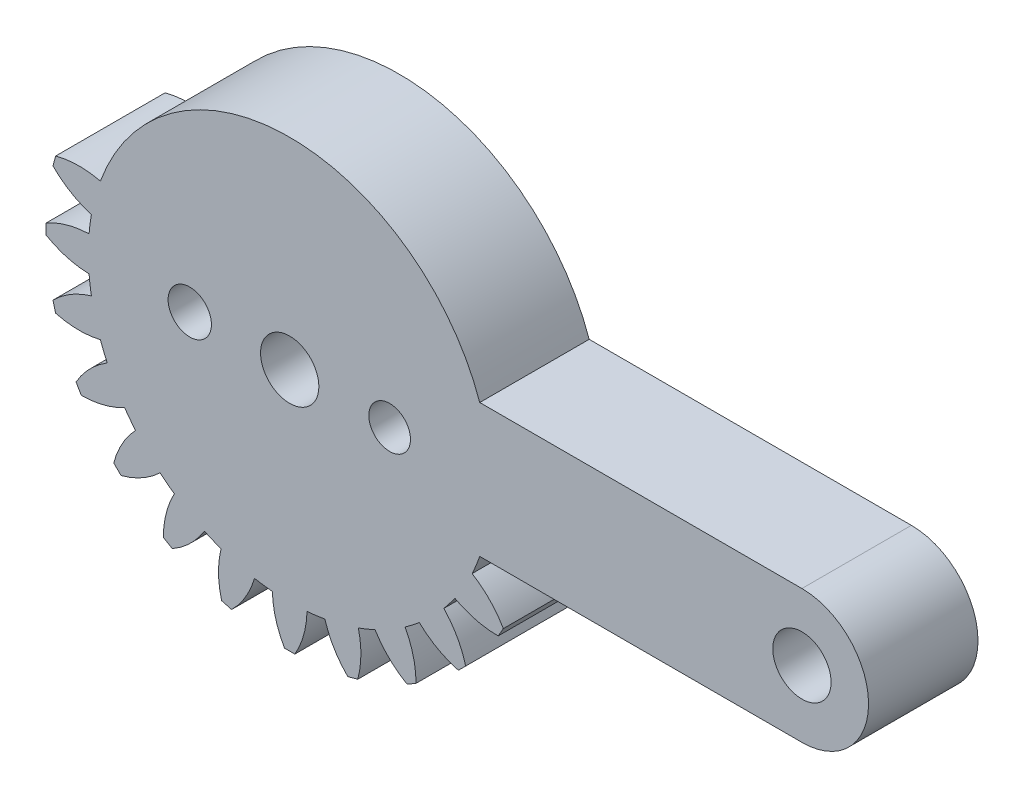
SolidWorks part; units mm, degrees
ref_plane "Front Plane" through (0, 0, 0) normal (0, 0, 1) x (1, 0, 0)
ref_plane "Top Plane" through (0, 0, 0) normal (0, 1, 0) x (1, 0, 0)
ref_plane "Right Plane" through (0, 0, 0) normal (1, 0, 0) x (0, 0, -1)
sketch "Sketch2" plane through (0, 0, 0) normal (0, 0, 1) x (1, 0, 0)
  line L0 (0, 0) -> (30.75, 0) construction
  line L1 (0, -14.63) -> (0, 14.63) construction
  line L2 (-0.31, 14.63) -> (0.31, 14.63)
  line L3 (3.4871, 14.2117) -> (4.086, 14.0513)
  line L4 (7.0465, 12.825) -> (7.5835, 12.515)
  line L5 (10.1258, 10.5642) -> (10.5642, 10.1258)
  line L6 (12.515, 7.5835) -> (12.825, 7.0465)
  line L7 (14.0513, 4.086) -> (14.2117, 3.4871)
  line L8 (14.63, 0.31) -> (14.63, -0.31)
  line L9 (14.2117, -3.4871) -> (14.0513, -4.086)
  line L10 (12.825, -7.0465) -> (12.515, -7.5835)
  line L11 (10.5642, -10.1258) -> (10.1258, -10.5642)
  line L12 (7.5835, -12.515) -> (7.0465, -12.825)
  line L13 (4.086, -14.0513) -> (3.4871, -14.2117)
  line L14 (0.31, -14.63) -> (-0.31, -14.63)
  line L15 (-3.4871, -14.2117) -> (-4.086, -14.0513)
  line L16 (-7.0465, -12.825) -> (-7.5835, -12.515)
  line L17 (-10.1258, -10.5642) -> (-10.5642, -10.1258)
  line L18 (-12.515, -7.5835) -> (-12.825, -7.0465)
  line L19 (-14.0513, -4.086) -> (-14.2117, -3.4871)
  line L20 (-14.63, -0.31) -> (-14.63, 0.31)
  line L21 (-14.2117, 3.4871) -> (-14.0513, 4.086)
  line L22 (-12.825, 7.0465) -> (-12.515, 7.5835)
  line L23 (-10.5642, 10.1258) -> (-10.1258, 10.5642)
  line L24 (-7.5835, 12.515) -> (-7.0465, 12.825)
  line L25 (-4.086, 14.0513) -> (-3.4871, 14.2117)
  line L26 (30.75, -4) -> (30.75, 4) construction
  line L27 (30.75, 4) -> (11.4091, 4)
  line L28 (30.75, -4) -> (11.4091, -4)
  circle A0 centre (0, 0) radius 1.75
  circle A1 centre (0, 0) radius 12.09
  circle A2 centre (30.75, 0) radius 1.75
  arc A3 (-1.04, 12.0452) -> (-0.31, 14.63) centre (4.3585, 11.9161) cw
  arc A4 (1.04, 12.0452) -> (0.31, 14.63) centre (-4.3585, 11.9161) ccw
  arc A5 (4.1221, 11.3656) -> (4.086, 14.0513) centre (-1.1258, 12.6381) ccw
  arc A6 (2.113, 11.9039) -> (3.4871, 14.2117) centre (7.294, 10.382) cw
  arc A7 (6.9233, 9.9114) -> (7.5835, 12.515) centre (2.1835, 12.4988) ccw
  arc A8 (5.1219, 10.9514) -> (7.0465, 12.825) centre (9.7326, 8.1404) cw
  arc A9 (9.2526, 7.7818) -> (10.5642, 10.1258) centre (5.344, 11.5078) ccw
  arc A10 (7.7818, 9.2526) -> (10.1258, 10.5642) centre (11.5078, 5.344) cw
  arc A11 (10.9514, 5.1219) -> (12.825, 7.0465) centre (8.1404, 9.7326) ccw
  arc A12 (9.9114, 6.9233) -> (12.515, 7.5835) centre (12.4988, 2.1835) cw
  arc A13 (11.9039, 2.113) -> (14.2117, 3.4871) centre (10.382, 7.294) ccw
  arc A14 (11.3656, 4.1221) -> (14.0513, 4.086) centre (12.6381, -1.1258) cw
  arc A15 (12.0452, -1.04) -> (14.63, -0.31) centre (11.9161, 4.3585) ccw
  arc A16 (12.0452, 1.04) -> (14.63, 0.31) centre (11.9161, -4.3585) cw
  arc A17 (11.3656, -4.1221) -> (14.0513, -4.086) centre (12.6381, 1.1258) ccw
  arc A18 (11.9039, -2.113) -> (14.2117, -3.4871) centre (10.382, -7.294) cw
  arc A19 (9.9114, -6.9233) -> (12.515, -7.5835) centre (12.4988, -2.1835) ccw
  arc A20 (10.9514, -5.1219) -> (12.825, -7.0465) centre (8.1404, -9.7326) cw
  arc A21 (7.7818, -9.2526) -> (10.1258, -10.5642) centre (11.5078, -5.344) ccw
  arc A22 (9.2526, -7.7818) -> (10.5642, -10.1258) centre (5.344, -11.5078) cw
  arc A23 (5.1219, -10.9514) -> (7.0465, -12.825) centre (9.7326, -8.1404) ccw
  arc A24 (6.9233, -9.9114) -> (7.5835, -12.515) centre (2.1835, -12.4988) cw
  arc A25 (2.113, -11.9039) -> (3.4871, -14.2117) centre (7.294, -10.382) ccw
  arc A26 (4.1221, -11.3656) -> (4.086, -14.0513) centre (-1.1258, -12.6381) cw
  arc A27 (-1.04, -12.0452) -> (-0.31, -14.63) centre (4.3585, -11.9161) ccw
  arc A28 (1.04, -12.0452) -> (0.31, -14.63) centre (-4.3585, -11.9161) cw
  arc A29 (-4.1221, -11.3656) -> (-4.086, -14.0513) centre (1.1258, -12.6381) ccw
  arc A30 (-2.113, -11.9039) -> (-3.4871, -14.2117) centre (-7.294, -10.382) cw
  arc A31 (-6.9233, -9.9114) -> (-7.5835, -12.515) centre (-2.1835, -12.4988) ccw
  arc A32 (-5.1219, -10.9514) -> (-7.0465, -12.825) centre (-9.7326, -8.1404) cw
  arc A33 (-9.2526, -7.7818) -> (-10.5642, -10.1258) centre (-5.344, -11.5078) ccw
  arc A34 (-7.7818, -9.2526) -> (-10.1258, -10.5642) centre (-11.5078, -5.344) cw
  arc A35 (-10.9514, -5.1219) -> (-12.825, -7.0465) centre (-8.1404, -9.7326) ccw
  arc A36 (-9.9114, -6.9233) -> (-12.515, -7.5835) centre (-12.4988, -2.1835) cw
  arc A37 (-11.9039, -2.113) -> (-14.2117, -3.4871) centre (-10.382, -7.294) ccw
  arc A38 (-11.3656, -4.1221) -> (-14.0513, -4.086) centre (-12.6381, 1.1258) cw
  arc A39 (-12.0452, 1.04) -> (-14.63, 0.31) centre (-11.9161, -4.3585) ccw
  arc A40 (-12.0452, -1.04) -> (-14.63, -0.31) centre (-11.9161, 4.3585) cw
  arc A41 (-11.3656, 4.1221) -> (-14.0513, 4.086) centre (-12.6381, -1.1258) ccw
  arc A42 (-11.9039, 2.113) -> (-14.2117, 3.4871) centre (-10.382, 7.294) cw
  arc A43 (-9.9114, 6.9233) -> (-12.515, 7.5835) centre (-12.4988, 2.1835) ccw
  arc A44 (-10.9514, 5.1219) -> (-12.825, 7.0465) centre (-8.1404, 9.7326) cw
  arc A45 (-7.7818, 9.2526) -> (-10.1258, 10.5642) centre (-11.5078, 5.344) ccw
  arc A46 (-9.2526, 7.7818) -> (-10.5642, 10.1258) centre (-5.344, 11.5078) cw
  arc A47 (-5.1219, 10.9514) -> (-7.0465, 12.825) centre (-9.7326, 8.1404) ccw
  arc A48 (-6.9233, 9.9114) -> (-7.5835, 12.515) centre (-2.1835, 12.4988) cw
  arc A49 (-2.113, 11.9039) -> (-3.4871, 14.2117) centre (-7.294, 10.382) ccw
  arc A50 (-4.1221, 11.3656) -> (-4.086, 14.0513) centre (1.1258, 12.6381) cw
  arc A51 (30.75, -4) -> (30.75, 4) centre (30.75, 0) ccw
  point P9 (0, 0)
  point P156 (0, 0)
  point P158 (30.75, 0)
  dimension "D2" = 3.5
  dimension "D3" = 3.5
  dimension "D4" = 24.18
  dimension "D6" = 5.4
  dimension "D10" = 8
  dimension "D1" = 30.75
  dimension "D5" = 29.26
  dimension "D7" = 0.31
  dimension "D8" = 1.04
  dimension "D9" = 24
extrude "Boss-Extrude1" add sketch "Sketch2" against normal blind 12 contours A1 | L28 A51 L27 L7 A13 A1 A16 L8 A15 A18 L9 A2 | A28 A1 A27 L14 | A30 A1 A29 L15 | A32 A1 A31 L16 | A34 A1 A33 L17 | A36 A1 A35 L18 | A38 A1 A37 L19 | A40 A1 A39 L20 | A42 A1 A41 L21 | A26 A1 A25 L13 | A24 A1 A23 L12 | A22 A1 A21 L11 | A20 A1 A19 L10 | A18 A1 L28 L9 | A16 A1 A15 L8 | A1 A13 L7 L27 region at (0, 11.748, 0) region at (-12.7103, 3.4057, 0) region at (12.7154, 3.2861, 0) region at (-13.1586, 0, 0) region at (23.1147, 0, 0) region at (13.1586, 0, 0) region at (-12.7103, -3.4057, 0) region at (12.7154, -3.2861, 0) region at (-11.3957, -6.5793, 0) region at (-9.3046, -9.3046, 0) region at (11.3957, -6.5793, 0) region at (-6.5793, -11.3957, 0) region at (9.3046, -9.3046, 0) region at (-3.4057, -12.7103, 0) region at (6.5793, -11.3957, 0) region at (0, -13.1586, 0) region at (3.4057, -12.7103, 0)
sketch "Sketch10" plane through (0, 0, -12) normal (0, 0, -1) x (-1, 0, 0)
  line L0 (0, 0) -> (-6, 0) construction
  line L1 (-6, 0) -> (6, 0) construction
  circle A0 centre (6, 0) radius 1.3
  circle A1 centre (-6, 0) radius 1.25
  circle A3 centre (0, 0) radius 1.75 construction
  circle A4 centre (0, 0) radius 1.75
  dimension "D3" = 2.6
  dimension "D4" = 2.5
  dimension "D5" = 3.5
  dimension "D1" = 6
  dimension "D2" = 6
extrude "Cut-Extrude1" cut sketch "Sketch10" against normal through all contours A1 | A0 region at (-6, 0, -12) region at (6, 0, -12)
sketch "Sketch11" plane through (0, 0, -12) normal (0, 0, -1) x (-1, 0, 0)
  line L14 (-11.4091, 4) -> (-30.75, 4)
  line L15 (-30.75, -4) -> (-11.4091, -4)
  line L16 (-12.825, -7.0465) -> (-12.515, -7.5835)
  line L17 (-10.5642, -10.1258) -> (-10.1258, -10.5642)
  line L18 (-7.5835, -12.515) -> (-7.0465, -12.825)
  line L19 (-4.086, -14.0513) -> (-3.4871, -14.2117)
  line L20 (-0.31, -14.63) -> (0.31, -14.63)
  line L21 (3.4871, -14.2117) -> (4.086, -14.0513)
  line L22 (7.0465, -12.825) -> (7.5835, -12.515)
  line L23 (10.1258, -10.5642) -> (10.5642, -10.1258)
  line L24 (12.515, -7.5835) -> (12.825, -7.0465)
  line L25 (14.0513, -4.086) -> (14.2117, -3.4871)
  line L26 (14.63, -0.31) -> (14.63, 0.31)
  line L27 (14.2117, 3.4871) -> (14.0513, 4.086)
  line L28 (-11.4091, 4) -> (-30.75, 4)
  line L29 (-30.75, -4) -> (-11.4091, -4)
  line L30 (-12.825, -7.0465) -> (-12.515, -7.5835)
  line L31 (-10.5642, -10.1258) -> (-10.1258, -10.5642)
  line L32 (-7.5835, -12.515) -> (-7.0465, -12.825)
  line L33 (-4.086, -14.0513) -> (-3.4871, -14.2117)
  line L34 (-0.31, -14.63) -> (0.31, -14.63)
  line L35 (3.4871, -14.2117) -> (4.086, -14.0513)
  line L36 (7.0465, -12.825) -> (7.5835, -12.515)
  line L37 (10.1258, -10.5642) -> (10.5642, -10.1258)
  line L38 (12.515, -7.5835) -> (12.825, -7.0465)
  line L39 (14.0513, -4.086) -> (14.2117, -3.4871)
  line L40 (14.63, -0.31) -> (14.63, 0.31)
  line L41 (14.2117, 3.4871) -> (14.0513, 4.086)
  arc A38 (-30.75, 4) -> (-30.75, -4) centre (-30.75, 0) ccw
  arc A39 (-11.4091, -4) -> (-10.9514, -5.1219) centre (0, 0) ccw
  arc A40 (-10.9514, -5.1219) -> (-12.825, -7.0465) centre (-8.1404, -9.7326) ccw
  arc A41 (-12.515, -7.5835) -> (-9.9114, -6.9233) centre (-12.4988, -2.1835) ccw
  arc A42 (-9.9114, -6.9233) -> (-9.2526, -7.7818) centre (0, 0) ccw
  arc A43 (-9.2526, -7.7818) -> (-10.5642, -10.1258) centre (-5.344, -11.5078) ccw
  arc A44 (-10.1258, -10.5642) -> (-7.7818, -9.2526) centre (-11.5078, -5.344) ccw
  arc A45 (-7.7818, -9.2526) -> (-6.9233, -9.9114) centre (0, 0) ccw
  arc A46 (-6.9233, -9.9114) -> (-7.5835, -12.515) centre (-2.1835, -12.4988) ccw
  arc A47 (-7.0465, -12.825) -> (-5.1219, -10.9514) centre (-9.7326, -8.1404) ccw
  arc A48 (-5.1219, -10.9514) -> (-4.1221, -11.3656) centre (0, 0) ccw
  arc A49 (-4.1221, -11.3656) -> (-4.086, -14.0513) centre (1.1258, -12.6381) ccw
  arc A50 (-3.4871, -14.2117) -> (-2.113, -11.9039) centre (-7.294, -10.382) ccw
  arc A51 (-2.113, -11.9039) -> (-1.04, -12.0452) centre (0, 0) ccw
  arc A52 (-1.04, -12.0452) -> (-0.31, -14.63) centre (4.3585, -11.9161) ccw
  arc A53 (0.31, -14.63) -> (1.04, -12.0452) centre (-4.3585, -11.9161) ccw
  arc A54 (1.04, -12.0452) -> (2.113, -11.9039) centre (0, 0) ccw
  arc A55 (2.113, -11.9039) -> (3.4871, -14.2117) centre (7.294, -10.382) ccw
  arc A56 (4.086, -14.0513) -> (4.1221, -11.3656) centre (-1.1258, -12.6381) ccw
  arc A57 (4.1221, -11.3656) -> (5.1219, -10.9514) centre (0, 0) ccw
  arc A58 (5.1219, -10.9514) -> (7.0465, -12.825) centre (9.7326, -8.1404) ccw
  arc A59 (7.5835, -12.515) -> (6.9233, -9.9114) centre (2.1835, -12.4988) ccw
  arc A60 (6.9233, -9.9114) -> (7.7818, -9.2526) centre (0, 0) ccw
  arc A61 (7.7818, -9.2526) -> (10.1258, -10.5642) centre (11.5078, -5.344) ccw
  arc A62 (10.5642, -10.1258) -> (9.2526, -7.7818) centre (5.344, -11.5078) ccw
  arc A63 (9.2526, -7.7818) -> (9.9114, -6.9233) centre (0, 0) ccw
  arc A64 (9.9114, -6.9233) -> (12.515, -7.5835) centre (12.4988, -2.1835) ccw
  arc A65 (12.825, -7.0465) -> (10.9514, -5.1219) centre (8.1404, -9.7326) ccw
  arc A66 (10.9514, -5.1219) -> (11.3656, -4.1221) centre (0, 0) ccw
  arc A67 (11.3656, -4.1221) -> (14.0513, -4.086) centre (12.6381, 1.1258) ccw
  arc A68 (14.2117, -3.4871) -> (11.9039, -2.113) centre (10.382, -7.294) ccw
  arc A69 (11.9039, -2.113) -> (12.0452, -1.04) centre (0, 0) ccw
  arc A70 (12.0452, -1.04) -> (14.63, -0.31) centre (11.9161, 4.3585) ccw
  arc A71 (14.63, 0.31) -> (12.0452, 1.04) centre (11.9161, -4.3585) ccw
  arc A72 (12.0452, 1.04) -> (11.9039, 2.113) centre (0, 0) ccw
  arc A73 (11.9039, 2.113) -> (14.2117, 3.4871) centre (10.382, 7.294) ccw
  arc A74 (14.0513, 4.086) -> (11.3656, 4.1221) centre (12.6381, -1.1258) ccw
  arc A75 (11.3656, 4.1221) -> (-11.4091, 4) centre (0, 0) ccw
  arc A76 (-30.75, 4) -> (-30.75, -4) centre (-30.75, 0) ccw
  arc A77 (-11.4091, -4) -> (-10.9514, -5.1219) centre (0, 0) ccw
  arc A78 (-10.9514, -5.1219) -> (-12.825, -7.0465) centre (-8.1404, -9.7326) ccw
  arc A79 (-12.515, -7.5835) -> (-9.9114, -6.9233) centre (-12.4988, -2.1835) ccw
  arc A80 (-9.9114, -6.9233) -> (-9.2526, -7.7818) centre (0, 0) ccw
  arc A81 (-9.2526, -7.7818) -> (-10.5642, -10.1258) centre (-5.344, -11.5078) ccw
  arc A82 (-10.1258, -10.5642) -> (-7.7818, -9.2526) centre (-11.5078, -5.344) ccw
  arc A83 (-7.7818, -9.2526) -> (-6.9233, -9.9114) centre (0, 0) ccw
  arc A84 (-6.9233, -9.9114) -> (-7.5835, -12.515) centre (-2.1835, -12.4988) ccw
  arc A85 (-7.0465, -12.825) -> (-5.1219, -10.9514) centre (-9.7326, -8.1404) ccw
  arc A86 (-5.1219, -10.9514) -> (-4.1221, -11.3656) centre (0, 0) ccw
  arc A87 (-4.1221, -11.3656) -> (-4.086, -14.0513) centre (1.1258, -12.6381) ccw
  arc A88 (-3.4871, -14.2117) -> (-2.113, -11.9039) centre (-7.294, -10.382) ccw
  arc A89 (-2.113, -11.9039) -> (-1.04, -12.0452) centre (0, 0) ccw
  arc A90 (-1.04, -12.0452) -> (-0.31, -14.63) centre (4.3585, -11.9161) ccw
  arc A91 (0.31, -14.63) -> (1.04, -12.0452) centre (-4.3585, -11.9161) ccw
  arc A92 (1.04, -12.0452) -> (2.113, -11.9039) centre (0, 0) ccw
  arc A93 (2.113, -11.9039) -> (3.4871, -14.2117) centre (7.294, -10.382) ccw
  arc A94 (4.086, -14.0513) -> (4.1221, -11.3656) centre (-1.1258, -12.6381) ccw
  arc A95 (4.1221, -11.3656) -> (5.1219, -10.9514) centre (0, 0) ccw
  arc A96 (5.1219, -10.9514) -> (7.0465, -12.825) centre (9.7326, -8.1404) ccw
  arc A97 (7.5835, -12.515) -> (6.9233, -9.9114) centre (2.1835, -12.4988) ccw
  arc A98 (6.9233, -9.9114) -> (7.7818, -9.2526) centre (0, 0) ccw
  arc A99 (7.7818, -9.2526) -> (10.1258, -10.5642) centre (11.5078, -5.344) ccw
  arc A100 (10.5642, -10.1258) -> (9.2526, -7.7818) centre (5.344, -11.5078) ccw
  arc A101 (9.2526, -7.7818) -> (9.9114, -6.9233) centre (0, 0) ccw
  arc A102 (9.9114, -6.9233) -> (12.515, -7.5835) centre (12.4988, -2.1835) ccw
  arc A103 (12.825, -7.0465) -> (10.9514, -5.1219) centre (8.1404, -9.7326) ccw
  arc A104 (10.9514, -5.1219) -> (11.3656, -4.1221) centre (0, 0) ccw
  arc A105 (11.3656, -4.1221) -> (14.0513, -4.086) centre (12.6381, 1.1258) ccw
  arc A106 (14.2117, -3.4871) -> (11.9039, -2.113) centre (10.382, -7.294) ccw
  arc A107 (11.9039, -2.113) -> (12.0452, -1.04) centre (0, 0) ccw
  arc A108 (12.0452, -1.04) -> (14.63, -0.31) centre (11.9161, 4.3585) ccw
  arc A109 (14.63, 0.31) -> (12.0452, 1.04) centre (11.9161, -4.3585) ccw
  arc A110 (12.0452, 1.04) -> (11.9039, 2.113) centre (0, 0) ccw
  arc A111 (11.9039, 2.113) -> (14.2117, 3.4871) centre (10.382, 7.294) ccw
  arc A112 (14.0513, 4.086) -> (11.3656, 4.1221) centre (12.6381, -1.1258) ccw
  arc A113 (11.3656, 4.1221) -> (-11.4091, 4) centre (0, 0) ccw
  dimension "D1" = 0
extrude "Cut-Extrude2" cut sketch "Sketch11" against normal blind 4
sketch "Sketch12" plane through (0, 0, 0) normal (0, 0, 1) x (1, 0, 0)
  line L14 (30.75, 4) -> (11.4091, 4)
  line L15 (-14.0513, 4.086) -> (-14.2117, 3.4871)
  line L16 (-14.63, 0.31) -> (-14.63, -0.31)
  line L17 (-14.2117, -3.4871) -> (-14.0513, -4.086)
  line L18 (-12.825, -7.0465) -> (-12.515, -7.5835)
  line L19 (-10.5642, -10.1258) -> (-10.1258, -10.5642)
  line L20 (-7.5835, -12.515) -> (-7.0465, -12.825)
  line L21 (-4.086, -14.0513) -> (-3.4871, -14.2117)
  line L22 (-0.31, -14.63) -> (0.31, -14.63)
  line L23 (3.4871, -14.2117) -> (4.086, -14.0513)
  line L24 (7.0465, -12.825) -> (7.5835, -12.515)
  line L25 (10.1258, -10.5642) -> (10.5642, -10.1258)
  line L26 (12.515, -7.5835) -> (12.825, -7.0465)
  line L27 (11.4091, -4) -> (30.75, -4)
  line L28 (30.75, 4) -> (11.4091, 4)
  line L29 (-14.0513, 4.086) -> (-14.2117, 3.4871)
  line L30 (-14.63, 0.31) -> (-14.63, -0.31)
  line L31 (-14.2117, -3.4871) -> (-14.0513, -4.086)
  line L32 (-12.825, -7.0465) -> (-12.515, -7.5835)
  line L33 (-10.5642, -10.1258) -> (-10.1258, -10.5642)
  line L34 (-7.5835, -12.515) -> (-7.0465, -12.825)
  line L35 (-4.086, -14.0513) -> (-3.4871, -14.2117)
  line L36 (-0.31, -14.63) -> (0.31, -14.63)
  line L37 (3.4871, -14.2117) -> (4.086, -14.0513)
  line L38 (7.0465, -12.825) -> (7.5835, -12.515)
  line L39 (10.1258, -10.5642) -> (10.5642, -10.1258)
  line L40 (12.515, -7.5835) -> (12.825, -7.0465)
  line L41 (11.4091, -4) -> (30.75, -4)
  arc A38 (11.4091, 4) -> (-11.3656, 4.1221) centre (0, 0) ccw
  arc A39 (-11.3656, 4.1221) -> (-14.0513, 4.086) centre (-12.6381, -1.1258) ccw
  arc A40 (-14.2117, 3.4871) -> (-11.9039, 2.113) centre (-10.382, 7.294) ccw
  arc A41 (-11.9039, 2.113) -> (-12.0452, 1.04) centre (0, 0) ccw
  arc A42 (-12.0452, 1.04) -> (-14.63, 0.31) centre (-11.9161, -4.3585) ccw
  arc A43 (-14.63, -0.31) -> (-12.0452, -1.04) centre (-11.9161, 4.3585) ccw
  arc A44 (-12.0452, -1.04) -> (-11.9039, -2.113) centre (0, 0) ccw
  arc A45 (-11.9039, -2.113) -> (-14.2117, -3.4871) centre (-10.382, -7.294) ccw
  arc A46 (-14.0513, -4.086) -> (-11.3656, -4.1221) centre (-12.6381, 1.1258) ccw
  arc A47 (-11.3656, -4.1221) -> (-10.9514, -5.1219) centre (0, 0) ccw
  arc A48 (-10.9514, -5.1219) -> (-12.825, -7.0465) centre (-8.1404, -9.7326) ccw
  arc A49 (-12.515, -7.5835) -> (-9.9114, -6.9233) centre (-12.4988, -2.1835) ccw
  arc A50 (-9.9114, -6.9233) -> (-9.2526, -7.7818) centre (0, 0) ccw
  arc A51 (-9.2526, -7.7818) -> (-10.5642, -10.1258) centre (-5.344, -11.5078) ccw
  arc A52 (-10.1258, -10.5642) -> (-7.7818, -9.2526) centre (-11.5078, -5.344) ccw
  arc A53 (-7.7818, -9.2526) -> (-6.9233, -9.9114) centre (0, 0) ccw
  arc A54 (-6.9233, -9.9114) -> (-7.5835, -12.515) centre (-2.1835, -12.4988) ccw
  arc A55 (-7.0465, -12.825) -> (-5.1219, -10.9514) centre (-9.7326, -8.1404) ccw
  arc A56 (-5.1219, -10.9514) -> (-4.1221, -11.3656) centre (0, 0) ccw
  arc A57 (-4.1221, -11.3656) -> (-4.086, -14.0513) centre (1.1258, -12.6381) ccw
  arc A58 (-3.4871, -14.2117) -> (-2.113, -11.9039) centre (-7.294, -10.382) ccw
  arc A59 (-2.113, -11.9039) -> (-1.04, -12.0452) centre (0, 0) ccw
  arc A60 (-1.04, -12.0452) -> (-0.31, -14.63) centre (4.3585, -11.9161) ccw
  arc A61 (0.31, -14.63) -> (1.04, -12.0452) centre (-4.3585, -11.9161) ccw
  arc A62 (1.04, -12.0452) -> (2.113, -11.9039) centre (0, 0) ccw
  arc A63 (2.113, -11.9039) -> (3.4871, -14.2117) centre (7.294, -10.382) ccw
  arc A64 (4.086, -14.0513) -> (4.1221, -11.3656) centre (-1.1258, -12.6381) ccw
  arc A65 (4.1221, -11.3656) -> (5.1219, -10.9514) centre (0, 0) ccw
  arc A66 (5.1219, -10.9514) -> (7.0465, -12.825) centre (9.7326, -8.1404) ccw
  arc A67 (7.5835, -12.515) -> (6.9233, -9.9114) centre (2.1835, -12.4988) ccw
  arc A68 (6.9233, -9.9114) -> (7.7818, -9.2526) centre (0, 0) ccw
  arc A69 (7.7818, -9.2526) -> (10.1258, -10.5642) centre (11.5078, -5.344) ccw
  arc A70 (10.5642, -10.1258) -> (9.2526, -7.7818) centre (5.344, -11.5078) ccw
  arc A71 (9.2526, -7.7818) -> (9.9114, -6.9233) centre (0, 0) ccw
  arc A72 (9.9114, -6.9233) -> (12.515, -7.5835) centre (12.4988, -2.1835) ccw
  arc A73 (12.825, -7.0465) -> (10.9514, -5.1219) centre (8.1404, -9.7326) ccw
  arc A74 (10.9514, -5.1219) -> (11.4091, -4) centre (0, 0) ccw
  arc A75 (30.75, -4) -> (30.75, 4) centre (30.75, 0) ccw
  arc A76 (11.4091, 4) -> (-11.3656, 4.1221) centre (0, 0) ccw
  arc A77 (-11.3656, 4.1221) -> (-14.0513, 4.086) centre (-12.6381, -1.1258) ccw
  arc A78 (-14.2117, 3.4871) -> (-11.9039, 2.113) centre (-10.382, 7.294) ccw
  arc A79 (-11.9039, 2.113) -> (-12.0452, 1.04) centre (0, 0) ccw
  arc A80 (-12.0452, 1.04) -> (-14.63, 0.31) centre (-11.9161, -4.3585) ccw
  arc A81 (-14.63, -0.31) -> (-12.0452, -1.04) centre (-11.9161, 4.3585) ccw
  arc A82 (-12.0452, -1.04) -> (-11.9039, -2.113) centre (0, 0) ccw
  arc A83 (-11.9039, -2.113) -> (-14.2117, -3.4871) centre (-10.382, -7.294) ccw
  arc A84 (-14.0513, -4.086) -> (-11.3656, -4.1221) centre (-12.6381, 1.1258) ccw
  arc A85 (-11.3656, -4.1221) -> (-10.9514, -5.1219) centre (0, 0) ccw
  arc A86 (-10.9514, -5.1219) -> (-12.825, -7.0465) centre (-8.1404, -9.7326) ccw
  arc A87 (-12.515, -7.5835) -> (-9.9114, -6.9233) centre (-12.4988, -2.1835) ccw
  arc A88 (-9.9114, -6.9233) -> (-9.2526, -7.7818) centre (0, 0) ccw
  arc A89 (-9.2526, -7.7818) -> (-10.5642, -10.1258) centre (-5.344, -11.5078) ccw
  arc A90 (-10.1258, -10.5642) -> (-7.7818, -9.2526) centre (-11.5078, -5.344) ccw
  arc A91 (-7.7818, -9.2526) -> (-6.9233, -9.9114) centre (0, 0) ccw
  arc A92 (-6.9233, -9.9114) -> (-7.5835, -12.515) centre (-2.1835, -12.4988) ccw
  arc A93 (-7.0465, -12.825) -> (-5.1219, -10.9514) centre (-9.7326, -8.1404) ccw
  arc A94 (-5.1219, -10.9514) -> (-4.1221, -11.3656) centre (0, 0) ccw
  arc A95 (-4.1221, -11.3656) -> (-4.086, -14.0513) centre (1.1258, -12.6381) ccw
  arc A96 (-3.4871, -14.2117) -> (-2.113, -11.9039) centre (-7.294, -10.382) ccw
  arc A97 (-2.113, -11.9039) -> (-1.04, -12.0452) centre (0, 0) ccw
  arc A98 (-1.04, -12.0452) -> (-0.31, -14.63) centre (4.3585, -11.9161) ccw
  arc A99 (0.31, -14.63) -> (1.04, -12.0452) centre (-4.3585, -11.9161) ccw
  arc A100 (1.04, -12.0452) -> (2.113, -11.9039) centre (0, 0) ccw
  arc A101 (2.113, -11.9039) -> (3.4871, -14.2117) centre (7.294, -10.382) ccw
  arc A102 (4.086, -14.0513) -> (4.1221, -11.3656) centre (-1.1258, -12.6381) ccw
  arc A103 (4.1221, -11.3656) -> (5.1219, -10.9514) centre (0, 0) ccw
  arc A104 (5.1219, -10.9514) -> (7.0465, -12.825) centre (9.7326, -8.1404) ccw
  arc A105 (7.5835, -12.515) -> (6.9233, -9.9114) centre (2.1835, -12.4988) ccw
  arc A106 (6.9233, -9.9114) -> (7.7818, -9.2526) centre (0, 0) ccw
  arc A107 (7.7818, -9.2526) -> (10.1258, -10.5642) centre (11.5078, -5.344) ccw
  arc A108 (10.5642, -10.1258) -> (9.2526, -7.7818) centre (5.344, -11.5078) ccw
  arc A109 (9.2526, -7.7818) -> (9.9114, -6.9233) centre (0, 0) ccw
  arc A110 (9.9114, -6.9233) -> (12.515, -7.5835) centre (12.4988, -2.1835) ccw
  arc A111 (12.825, -7.0465) -> (10.9514, -5.1219) centre (8.1404, -9.7326) ccw
  arc A112 (10.9514, -5.1219) -> (11.4091, -4) centre (0, 0) ccw
  arc A113 (30.75, -4) -> (30.75, 4) centre (30.75, 0) ccw
  dimension "D1" = 0
extrude "Cut-Extrude3" cut sketch "Sketch12" against normal blind 0.57 contours L41 A113 L28 A76 A77 L29 A78 A79 A80 L30 A81 A82 A83 L31 A84 A85 A86 L32 A87 A88 A89 L33 A90 A91 A92 L34 A93 A94 A95 L35 A96 A97 A98 L36 A99 A100 A101 L37 A102 A103 A104 L38 A105 A106 A107 L39 A108 A109 A110 L40 A111 region at (5.6718, -0.5498, 0)
sketch "Sketch15" plane through (0, -4, 0) normal (0, -1, 0) x (1, 0, 0)
  line L0 (32.5, -0.57) -> (32.5, -8) construction
sketch "Sketch16" plane through (0, 0, -0.57) normal (0, 0, 1) x (1, 0, 0)
  line L14 (11.4091, -4) -> (30.75, -4)
  line L15 (30.75, 4) -> (11.4091, 4)
  line L16 (-14.0513, 4.086) -> (-14.2117, 3.4871)
  line L17 (-14.63, 0.31) -> (-14.63, -0.31)
  line L18 (-14.2117, -3.4871) -> (-14.0513, -4.086)
  line L19 (-12.825, -7.0465) -> (-12.515, -7.5835)
  line L20 (-10.5642, -10.1258) -> (-10.1258, -10.5642)
  line L21 (-7.5835, -12.515) -> (-7.0465, -12.825)
  line L22 (-4.086, -14.0513) -> (-3.4871, -14.2117)
  line L23 (-0.31, -14.63) -> (0.31, -14.63)
  line L24 (3.4871, -14.2117) -> (4.086, -14.0513)
  line L25 (7.0465, -12.825) -> (7.5835, -12.515)
  line L26 (10.1258, -10.5642) -> (10.5642, -10.1258)
  line L27 (12.515, -7.5835) -> (12.825, -7.0465)
  line L28 (11.4091, -4) -> (30.75, -4)
  line L29 (30.75, 4) -> (11.4091, 4)
  line L30 (-14.0513, 4.086) -> (-14.2117, 3.4871)
  line L31 (-14.63, 0.31) -> (-14.63, -0.31)
  line L32 (-14.2117, -3.4871) -> (-14.0513, -4.086)
  line L33 (-12.825, -7.0465) -> (-12.515, -7.5835)
  line L34 (-10.5642, -10.1258) -> (-10.1258, -10.5642)
  line L35 (-7.5835, -12.515) -> (-7.0465, -12.825)
  line L36 (-4.086, -14.0513) -> (-3.4871, -14.2117)
  line L37 (-0.31, -14.63) -> (0.31, -14.63)
  line L38 (3.4871, -14.2117) -> (4.086, -14.0513)
  line L39 (7.0465, -12.825) -> (7.5835, -12.515)
  line L40 (10.1258, -10.5642) -> (10.5642, -10.1258)
  line L41 (12.515, -7.5835) -> (12.825, -7.0465)
  arc A38 (30.75, -4) -> (30.75, 4) centre (30.75, 0) ccw
  arc A39 (11.4091, 4) -> (-11.3656, 4.1221) centre (0, 0) ccw
  arc A40 (-11.3656, 4.1221) -> (-14.0513, 4.086) centre (-12.6381, -1.1258) ccw
  arc A41 (-14.2117, 3.4871) -> (-11.9039, 2.113) centre (-10.382, 7.294) ccw
  arc A42 (-11.9039, 2.113) -> (-12.0452, 1.04) centre (0, 0) ccw
  arc A43 (-12.0452, 1.04) -> (-14.63, 0.31) centre (-11.9161, -4.3585) ccw
  arc A44 (-14.63, -0.31) -> (-12.0452, -1.04) centre (-11.9161, 4.3585) ccw
  arc A45 (-12.0452, -1.04) -> (-11.9039, -2.113) centre (0, 0) ccw
  arc A46 (-11.9039, -2.113) -> (-14.2117, -3.4871) centre (-10.382, -7.294) ccw
  arc A47 (-14.0513, -4.086) -> (-11.3656, -4.1221) centre (-12.6381, 1.1258) ccw
  arc A48 (-11.3656, -4.1221) -> (-10.9514, -5.1219) centre (0, 0) ccw
  arc A49 (-10.9514, -5.1219) -> (-12.825, -7.0465) centre (-8.1404, -9.7326) ccw
  arc A50 (-12.515, -7.5835) -> (-9.9114, -6.9233) centre (-12.4988, -2.1835) ccw
  arc A51 (-9.9114, -6.9233) -> (-9.2526, -7.7818) centre (0, 0) ccw
  arc A52 (-9.2526, -7.7818) -> (-10.5642, -10.1258) centre (-5.344, -11.5078) ccw
  arc A53 (-10.1258, -10.5642) -> (-7.7818, -9.2526) centre (-11.5078, -5.344) ccw
  arc A54 (-7.7818, -9.2526) -> (-6.9233, -9.9114) centre (0, 0) ccw
  arc A55 (-6.9233, -9.9114) -> (-7.5835, -12.515) centre (-2.1835, -12.4988) ccw
  arc A56 (-7.0465, -12.825) -> (-5.1219, -10.9514) centre (-9.7326, -8.1404) ccw
  arc A57 (-5.1219, -10.9514) -> (-4.1221, -11.3656) centre (0, 0) ccw
  arc A58 (-4.1221, -11.3656) -> (-4.086, -14.0513) centre (1.1258, -12.6381) ccw
  arc A59 (-3.4871, -14.2117) -> (-2.113, -11.9039) centre (-7.294, -10.382) ccw
  arc A60 (-2.113, -11.9039) -> (-1.04, -12.0452) centre (0, 0) ccw
  arc A61 (-1.04, -12.0452) -> (-0.31, -14.63) centre (4.3585, -11.9161) ccw
  arc A62 (0.31, -14.63) -> (1.04, -12.0452) centre (-4.3585, -11.9161) ccw
  arc A63 (1.04, -12.0452) -> (2.113, -11.9039) centre (0, 0) ccw
  arc A64 (2.113, -11.9039) -> (3.4871, -14.2117) centre (7.294, -10.382) ccw
  arc A65 (4.086, -14.0513) -> (4.1221, -11.3656) centre (-1.1258, -12.6381) ccw
  arc A66 (4.1221, -11.3656) -> (5.1219, -10.9514) centre (0, 0) ccw
  arc A67 (5.1219, -10.9514) -> (7.0465, -12.825) centre (9.7326, -8.1404) ccw
  arc A68 (7.5835, -12.515) -> (6.9233, -9.9114) centre (2.1835, -12.4988) ccw
  arc A69 (6.9233, -9.9114) -> (7.7818, -9.2526) centre (0, 0) ccw
  arc A70 (7.7818, -9.2526) -> (10.1258, -10.5642) centre (11.5078, -5.344) ccw
  arc A71 (10.5642, -10.1258) -> (9.2526, -7.7818) centre (5.344, -11.5078) ccw
  arc A72 (9.2526, -7.7818) -> (9.9114, -6.9233) centre (0, 0) ccw
  arc A73 (9.9114, -6.9233) -> (12.515, -7.5835) centre (12.4988, -2.1835) ccw
  arc A74 (12.825, -7.0465) -> (10.9514, -5.1219) centre (8.1404, -9.7326) ccw
  arc A75 (10.9514, -5.1219) -> (11.4091, -4) centre (0, 0) ccw
  arc A76 (30.75, -4) -> (30.75, 4) centre (30.75, 0) ccw
  arc A77 (11.4091, 4) -> (-11.3656, 4.1221) centre (0, 0) ccw
  arc A78 (-11.3656, 4.1221) -> (-14.0513, 4.086) centre (-12.6381, -1.1258) ccw
  arc A79 (-14.2117, 3.4871) -> (-11.9039, 2.113) centre (-10.382, 7.294) ccw
  arc A80 (-11.9039, 2.113) -> (-12.0452, 1.04) centre (0, 0) ccw
  arc A81 (-12.0452, 1.04) -> (-14.63, 0.31) centre (-11.9161, -4.3585) ccw
  arc A82 (-14.63, -0.31) -> (-12.0452, -1.04) centre (-11.9161, 4.3585) ccw
  arc A83 (-12.0452, -1.04) -> (-11.9039, -2.113) centre (0, 0) ccw
  arc A84 (-11.9039, -2.113) -> (-14.2117, -3.4871) centre (-10.382, -7.294) ccw
  arc A85 (-14.0513, -4.086) -> (-11.3656, -4.1221) centre (-12.6381, 1.1258) ccw
  arc A86 (-11.3656, -4.1221) -> (-10.9514, -5.1219) centre (0, 0) ccw
  arc A87 (-10.9514, -5.1219) -> (-12.825, -7.0465) centre (-8.1404, -9.7326) ccw
  arc A88 (-12.515, -7.5835) -> (-9.9114, -6.9233) centre (-12.4988, -2.1835) ccw
  arc A89 (-9.9114, -6.9233) -> (-9.2526, -7.7818) centre (0, 0) ccw
  arc A90 (-9.2526, -7.7818) -> (-10.5642, -10.1258) centre (-5.344, -11.5078) ccw
  arc A91 (-10.1258, -10.5642) -> (-7.7818, -9.2526) centre (-11.5078, -5.344) ccw
  arc A92 (-7.7818, -9.2526) -> (-6.9233, -9.9114) centre (0, 0) ccw
  arc A93 (-6.9233, -9.9114) -> (-7.5835, -12.515) centre (-2.1835, -12.4988) ccw
  arc A94 (-7.0465, -12.825) -> (-5.1219, -10.9514) centre (-9.7326, -8.1404) ccw
  arc A95 (-5.1219, -10.9514) -> (-4.1221, -11.3656) centre (0, 0) ccw
  arc A96 (-4.1221, -11.3656) -> (-4.086, -14.0513) centre (1.1258, -12.6381) ccw
  arc A97 (-3.4871, -14.2117) -> (-2.113, -11.9039) centre (-7.294, -10.382) ccw
  arc A98 (-2.113, -11.9039) -> (-1.04, -12.0452) centre (0, 0) ccw
  arc A99 (-1.04, -12.0452) -> (-0.31, -14.63) centre (4.3585, -11.9161) ccw
  arc A100 (0.31, -14.63) -> (1.04, -12.0452) centre (-4.3585, -11.9161) ccw
  arc A101 (1.04, -12.0452) -> (2.113, -11.9039) centre (0, 0) ccw
  arc A102 (2.113, -11.9039) -> (3.4871, -14.2117) centre (7.294, -10.382) ccw
  arc A103 (4.086, -14.0513) -> (4.1221, -11.3656) centre (-1.1258, -12.6381) ccw
  arc A104 (4.1221, -11.3656) -> (5.1219, -10.9514) centre (0, 0) ccw
  arc A105 (5.1219, -10.9514) -> (7.0465, -12.825) centre (9.7326, -8.1404) ccw
  arc A106 (7.5835, -12.515) -> (6.9233, -9.9114) centre (2.1835, -12.4988) ccw
  arc A107 (6.9233, -9.9114) -> (7.7818, -9.2526) centre (0, 0) ccw
  arc A108 (7.7818, -9.2526) -> (10.1258, -10.5642) centre (11.5078, -5.344) ccw
  arc A109 (10.5642, -10.1258) -> (9.2526, -7.7818) centre (5.344, -11.5078) ccw
  arc A110 (9.2526, -7.7818) -> (9.9114, -6.9233) centre (0, 0) ccw
  arc A111 (9.9114, -6.9233) -> (12.515, -7.5835) centre (12.4988, -2.1835) ccw
  arc A112 (12.825, -7.0465) -> (10.9514, -5.1219) centre (8.1404, -9.7326) ccw
  arc A113 (10.9514, -5.1219) -> (11.4091, -4) centre (0, 0) ccw
  dimension "D1" = 0
extrude "Cut-Extrude4" cut sketch "Sketch16" against normal blind 0.86
